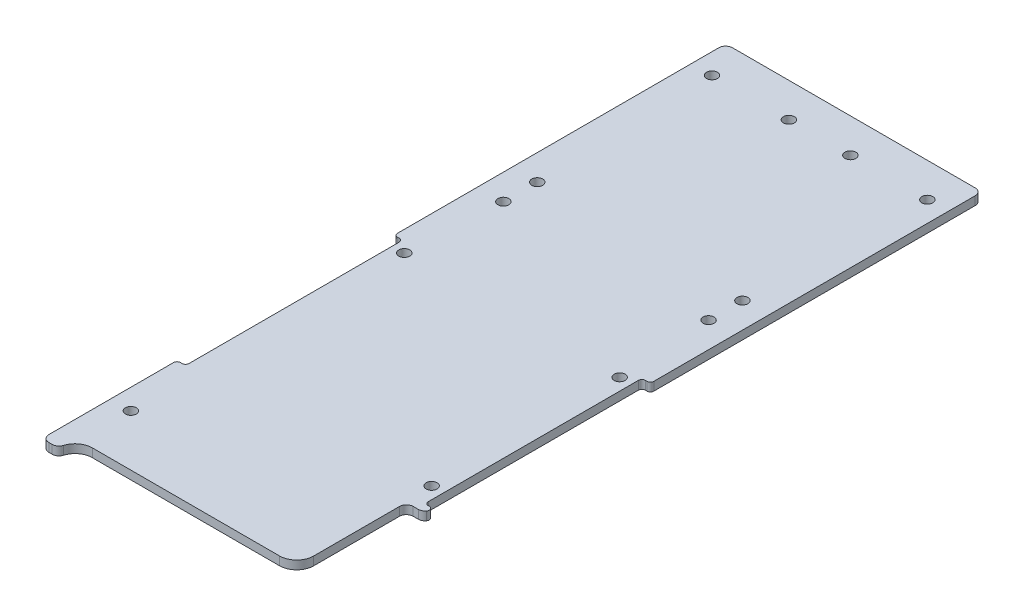
SolidWorks part; units mm, degrees
ref_plane "Front Plane" through (0, 0, 0) normal (0, 0, 1) x (1, 0, 0)
ref_plane "Top Plane" through (0, 0, 0) normal (0, 1, 0) x (1, 0, 0)
ref_plane "Right Plane" through (0, 0, 0) normal (1, 0, 0) x (0, 0, -1)
sketch "Sketch1" plane through (0, 0, 0) normal (0, 1, 0) x (1, 0, 0)
  line L0 (-39.9997, 0) -> (-39.9997, 114.3) construction
  line L1 (-47.625, 127) -> (47.625, 127)
  line L2 (-47.625, 127) -> (-47.625, -127)
  line L3 (-47.625, -127) -> (47.625, -127)
  line L4 (47.625, 127) -> (47.625, -127)
  line L5 (-47.625, 127) -> (47.625, -127) construction
  line L6 (-47.625, -127) -> (47.625, 127) construction
  line L7 (0, 0) -> (0, 127) construction
  line L8 (-39.9997, 0) -> (-39.9997, -101.6) construction
  line L9 (-39.9997, 0) -> (0, 0) construction
  line L10 (-41.275, -127) -> (-41.275, -120.65)
  line L11 (-41.275, -120.65) -> (41.275, -120.65)
  line L12 (41.275, -120.65) -> (41.275, -127)
  line L13 (-39.9997, 114.3) -> (-11.4247, 114.3) construction
  line L14 (39.9997, 114.3) -> (11.4247, 114.3) construction
  circle A0 centre (-39.9997, 114.3) radius 2.032
  circle A1 centre (-39.9997, 0) radius 2.032
  circle A2 centre (-39.9997, -101.6) radius 2.032
  circle A3 centre (39.9997, -101.6) radius 2.032
  circle A4 centre (39.9997, 0) radius 2.032
  circle A5 centre (39.9997, 114.3) radius 2.032
  circle A6 centre (-11.4247, 114.3) radius 2.032
  circle A7 centre (11.4247, 114.3) radius 2.032
  circle A8 centre (-39.9997, -69.85) radius 2.032
  circle A9 centre (39.9997, -69.85) radius 2.032
  point P0 (0, 0)
  dimension "D4" = 4.064
  dimension "D10" = 28.575
  dimension "D1" = 95.25
  dimension "D2" = 254
  dimension "D3" = 7.6253
  dimension "D5" = 12.7
  dimension "D6" = 25.4
  dimension "D7" = 6.35
  dimension "D8" = 6.35
  dimension "D9" = 6.35
  dimension "D11" = 69.85
extrude "Boss-Extrude1" add sketch "Sketch1" along normal blind 3.175 contours L4 L1 L2 L3 A4 A0 A1 A2 A3 A5 | A8 | A3 region at (0, 0, -2.6944) region at (39.9997, 0, 101.6) region at (-39.9997, 0, 69.85)
fillet "Fillet1" radius 2.54 4 edges at (-47.625, 1.5875, -127) (47.625, 1.5875, -127) (47.625, 1.5875, 127) (-47.625, 1.5875, 127)
fillet "Fillet2" radius 2.54 2 edges at (41.275, 1.5875, 127) (-41.275, 1.5875, 127)
fillet "Fillet3" radius 6.35 2 edges at (41.275, 1.5875, 120.65) (-41.275, 1.5875, 120.65)
sketch "Sketch2" plane through (0, 0, 0) normal (0, -1, 0) x (1, 0, 0)
  line L1 (43.815, 127) -> (45.085, 127) construction
  line L2 (40.6451, 123.5787) -> (40.6451, 79.8881)
  line L3 (40.6451, 79.8881) -> (47.625, 79.8881)
  line L11 (47.625, -124.46) -> (47.625, 124.46) construction
  line L12 (43.815, 127) -> (45.085, 127)
  line L13 (47.625, 79.8881) -> (47.625, 124.46)
  arc A0 (35.2956, 120.65) -> (41.3809, 125.1857) centre (35.2956, 127) ccw construction
  arc A1 (43.815, 127) -> (41.3809, 125.1857) centre (43.815, 124.46) ccw construction
  arc A2 (47.625, 124.46) -> (45.085, 127) centre (45.085, 124.46) ccw construction
  arc A3 (40.6451, 123.5787) -> (41.3809, 125.1857) centre (35.2956, 127) ccw
  arc A4 (43.815, 127) -> (41.3809, 125.1857) centre (43.815, 124.46) ccw
  arc A5 (47.625, 124.46) -> (45.085, 127) centre (45.085, 124.46) ccw
  point P0 (47.625, 77.7625)
  dimension "D2" = 47.1119
  dimension "D1" = 6.9799
extrude "Cut-Extrude1" cut sketch "Sketch2" against normal through all
fillet "Fillet4" radius 6.35 1 edges at (40.6451, 1.5875, 123.5787)
fillet "Fillet5" radius 2.54 2 edges at (47.625, 1.5875, 79.8881) (40.6451, 1.5875, 79.8881)
sketch "Sketch3" plane through (0, 0, 0) normal (0, -1, 0) x (1, 0, 0)
  line L0 (-36.3065, -49.7791) -> (-39.9133, -49.7791) construction
  line L1 (-40.4213, -49.276) -> (-40.4213, -45.7043) construction
  line L2 (-35.7985, -45.7043) -> (-35.7985, -49.276) construction
  line L3 (-39.9133, -45.2013) -> (-36.3065, -45.2013) construction
  line L4 (-36.3065, -37.2027) -> (-39.9133, -37.2027) construction
  line L5 (-35.7985, -33.1279) -> (-35.7985, -36.6996) construction
  line L6 (-40.4213, -36.6996) -> (-40.4213, -33.1279) construction
  line L7 (-39.9133, -32.6249) -> (-36.3065, -32.6249) construction
  line L8 (36.2867, -32.6249) -> (39.8935, -32.6249) construction
  line L9 (40.4015, -33.1279) -> (40.4015, -36.6996) construction
  line L10 (39.8935, -37.2027) -> (36.2867, -37.2027) construction
  line L11 (35.7787, -36.6996) -> (35.7787, -33.1279) construction
  line L12 (36.2867, -45.2013) -> (39.8935, -45.2013) construction
  line L13 (35.7787, -49.276) -> (35.7787, -45.7043) construction
  line L14 (40.4015, -45.7043) -> (40.4015, -49.276) construction
  line L15 (39.8935, -49.7791) -> (36.2867, -49.7791) construction
  line L16 (-36.3065, -49.7791) -> (-39.9133, -49.7791)
  line L17 (-40.4213, -49.276) -> (-40.4213, -45.7043)
  line L18 (-35.7985, -45.7043) -> (-35.7985, -49.276)
  line L19 (-39.9133, -45.2013) -> (-36.3065, -45.2013)
  line L20 (-36.3065, -37.2027) -> (-39.9133, -37.2027)
  line L21 (-35.7985, -33.1279) -> (-35.7985, -36.6996)
  line L22 (-40.4213, -36.6996) -> (-40.4213, -33.1279)
  line L23 (-39.9133, -32.6249) -> (-36.3065, -32.6249)
  line L24 (36.2867, -32.6249) -> (39.8935, -32.6249)
  line L25 (40.4015, -33.1279) -> (40.4015, -36.6996)
  line L26 (39.8935, -37.2027) -> (36.2867, -37.2027)
  line L27 (35.7787, -36.6996) -> (35.7787, -33.1279)
  line L28 (36.2867, -45.2013) -> (39.8935, -45.2013)
  line L29 (35.7787, -49.276) -> (35.7787, -45.7043)
  line L30 (40.4015, -45.7043) -> (40.4015, -49.276)
  line L31 (39.8935, -49.7791) -> (36.2867, -49.7791)
  line L32 (-47.625, -25.836) -> (47.625, -25.836)
  line L33 (-47.625, -124.46) -> (-47.625, 124.46) construction
  line L34 (47.625, -124.46) -> (47.625, 77.3481) construction
  line L35 (0, -25.836) -> (0, -56.0686) construction
  line L1362 (-40.4213, -34.9138) -> (-35.7985, -34.9138)
  line L1857 (-38.1099, -32.6249) -> (-38.1099, -37.2027)
  line L1858 (-38.1099, -45.2013) -> (-38.1099, -49.7791)
  line L1859 (-40.4213, -47.4902) -> (-35.7985, -47.4902)
  circle A0 centre (-38.1099, -34.9138) radius 2.032
  circle A1 centre (-38.1099, -47.4902) radius 2.032
  circle A2 centre (38.1099, -47.4902) radius 2.032
  circle A3 centre (38.1099, -34.9138) radius 2.032
  ellipse E0 centre (-39.9133, -45.7043) end of major axis (-39.4053, -45.7043) minor radius 0.5031 (-39.9133, -45.2013) -> (-40.4213, -45.7043) ccw construction
  ellipse E1 centre (-39.9133, -49.276) end of major axis (-39.4053, -49.276) minor radius 0.5031 (-40.4213, -49.276) -> (-39.9133, -49.7791) ccw construction
  ellipse E6 centre (-36.3065, -49.276) end of major axis (-35.7985, -49.276) minor radius 0.5031 (-36.3065, -49.7791) -> (-35.7985, -49.276) ccw construction
  ellipse E7 centre (-36.3065, -45.7043) end of major axis (-35.7985, -45.7043) minor radius 0.5031 (-35.7985, -45.7043) -> (-36.3065, -45.2013) ccw construction
  ellipse E8 centre (-39.9133, -36.6996) end of major axis (-39.4053, -36.6996) minor radius 0.5031 (-40.4213, -36.6996) -> (-39.9133, -37.2027) ccw construction
  ellipse E9 centre (-36.3065, -36.6996) end of major axis (-35.7985, -36.6996) minor radius 0.5031 (-36.3065, -37.2027) -> (-35.7985, -36.6996) ccw construction
  ellipse E10 centre (-36.3065, -33.1279) end of major axis (-35.7985, -33.1279) minor radius 0.5031 (-35.7985, -33.1279) -> (-36.3065, -32.6249) ccw construction
  ellipse E11 centre (-39.9133, -33.1279) end of major axis (-39.4053, -33.1279) minor radius 0.5031 (-39.9133, -32.6249) -> (-40.4213, -33.1279) ccw construction
  ellipse E12 centre (39.8935, -33.1279) end of major axis (40.4015, -33.1279) minor radius 0.5031 (40.4015, -33.1279) -> (39.8935, -32.6249) ccw construction
  ellipse E13 centre (36.2867, -33.1279) end of major axis (36.7947, -33.1279) minor radius 0.5031 (36.2867, -32.6249) -> (35.7787, -33.1279) ccw construction
  ellipse E14 centre (39.8935, -36.6996) end of major axis (40.4015, -36.6996) minor radius 0.5031 (39.8935, -37.2027) -> (40.4015, -36.6996) ccw construction
  ellipse E15 centre (36.2867, -36.6996) end of major axis (36.7947, -36.6996) minor radius 0.5031 (35.7787, -36.6996) -> (36.2867, -37.2027) ccw construction
  ellipse E16 centre (36.2867, -45.7043) end of major axis (36.7947, -45.7043) minor radius 0.5031 (36.2867, -45.2013) -> (35.7787, -45.7043) ccw construction
  ellipse E17 centre (36.2867, -49.276) end of major axis (36.7947, -49.276) minor radius 0.5031 (35.7787, -49.276) -> (36.2867, -49.7791) ccw construction
  ellipse E18 centre (39.8935, -45.7043) end of major axis (40.4015, -45.7043) minor radius 0.5031 (40.4015, -45.7043) -> (39.8935, -45.2013) ccw construction
  ellipse E19 centre (39.8935, -49.276) end of major axis (40.4015, -49.276) minor radius 0.5031 (39.8935, -49.7791) -> (40.4015, -49.276) ccw construction
  ellipse E20 centre (-39.9133, -45.7043) end of major axis (-39.4053, -45.7043) minor radius 0.5031 (-39.9133, -45.2013) -> (-40.4213, -45.7043) ccw
  ellipse E21 centre (-39.9133, -49.276) end of major axis (-39.4053, -49.276) minor radius 0.5031 (-40.4213, -49.276) -> (-39.9133, -49.7791) ccw
  ellipse E22 centre (-36.3065, -49.276) end of major axis (-35.7985, -49.276) minor radius 0.5031 (-36.3065, -49.7791) -> (-35.7985, -49.276) ccw
  ellipse E23 centre (-36.3065, -45.7043) end of major axis (-35.7985, -45.7043) minor radius 0.5031 (-35.7985, -45.7043) -> (-36.3065, -45.2013) ccw
  ellipse E24 centre (-39.9133, -36.6996) end of major axis (-39.4053, -36.6996) minor radius 0.5031 (-40.4213, -36.6996) -> (-39.9133, -37.2027) ccw
  ellipse E25 centre (-36.3065, -36.6996) end of major axis (-35.7985, -36.6996) minor radius 0.5031 (-36.3065, -37.2027) -> (-35.7985, -36.6996) ccw
  ellipse E26 centre (-36.3065, -33.1279) end of major axis (-35.7985, -33.1279) minor radius 0.5031 (-35.7985, -33.1279) -> (-36.3065, -32.6249) ccw
  ellipse E27 centre (-39.9133, -33.1279) end of major axis (-39.4053, -33.1279) minor radius 0.5031 (-39.9133, -32.6249) -> (-40.4213, -33.1279) ccw
  ellipse E28 centre (39.8935, -33.1279) end of major axis (40.4015, -33.1279) minor radius 0.5031 (40.4015, -33.1279) -> (39.8935, -32.6249) ccw
  ellipse E29 centre (36.2867, -33.1279) end of major axis (36.7947, -33.1279) minor radius 0.5031 (36.2867, -32.6249) -> (35.7787, -33.1279) ccw
  ellipse E30 centre (39.8935, -36.6996) end of major axis (40.4015, -36.6996) minor radius 0.5031 (39.8935, -37.2027) -> (40.4015, -36.6996) ccw
  ellipse E31 centre (36.2867, -36.6996) end of major axis (36.7947, -36.6996) minor radius 0.5031 (35.7787, -36.6996) -> (36.2867, -37.2027) ccw
  ellipse E32 centre (36.2867, -45.7043) end of major axis (36.7947, -45.7043) minor radius 0.5031 (36.2867, -45.2013) -> (35.7787, -45.7043) ccw
  ellipse E33 centre (36.2867, -49.276) end of major axis (36.7947, -49.276) minor radius 0.5031 (35.7787, -49.276) -> (36.2867, -49.7791) ccw
  ellipse E34 centre (39.8935, -45.7043) end of major axis (40.4015, -45.7043) minor radius 0.5031 (40.4015, -45.7043) -> (39.8935, -45.2013) ccw
  ellipse E35 centre (39.8935, -49.276) end of major axis (40.4015, -49.276) minor radius 0.5031 (39.8935, -49.7791) -> (40.4015, -49.276) ccw
  dimension "D2" = 4.064
extrude "Cut-Extrude2" cut sketch "Sketch3" against normal through all contours A0 | A1 | A2 | A3
sketch "Sketch4" plane through (0, 3.175, 0) normal (0, 1, 0) x (1, 0, 0)
  line L11 (-47.625, 124.46) -> (-47.625, -124.46) construction
  line L12 (-47.625, -76.835) -> (-44.45, -76.835)
  line L13 (-47.625, -76.835) -> (-47.625, 3.81)
  line L15 (-47.625, 3.81) -> (-44.45, 3.81)
  line L16 (-44.45, -76.835) -> (-44.45, 3.81)
  line L17 (47.625, 124.46) -> (47.625, -77.3481) construction
  line L18 (47.625, -76.835) -> (44.45, -76.835)
  line L19 (47.625, -76.835) -> (47.625, 3.81)
  line L20 (47.625, 3.81) -> (44.45, 3.81)
  line L45 (44.45, -76.835) -> (44.45, 3.81)
  line L47 (43.1851, -79.8881) -> (45.085, -79.8881) construction
  point P12 (47.625, -70.6538)
  point P15 (0, 0)
  dimension "D1" = 3.175
  dimension "D2" = 80.645
  dimension "D3" = 3.0531
extrude "Cut-Extrude3" cut sketch "Sketch4" against normal through all and the other way through all
fillet "Fillet6" radius 1.27 8 edges at (-44.45, 1.5875, -3.81) (-47.625, 1.5875, -3.81) (-47.625, 1.5875, 76.835) (-44.45, 1.5875, 76.835) (44.45, 1.5875, 76.835) (47.625, 1.5875, 76.835) (44.45, 1.5875, -3.81) (47.625, 1.5875, -3.81)
